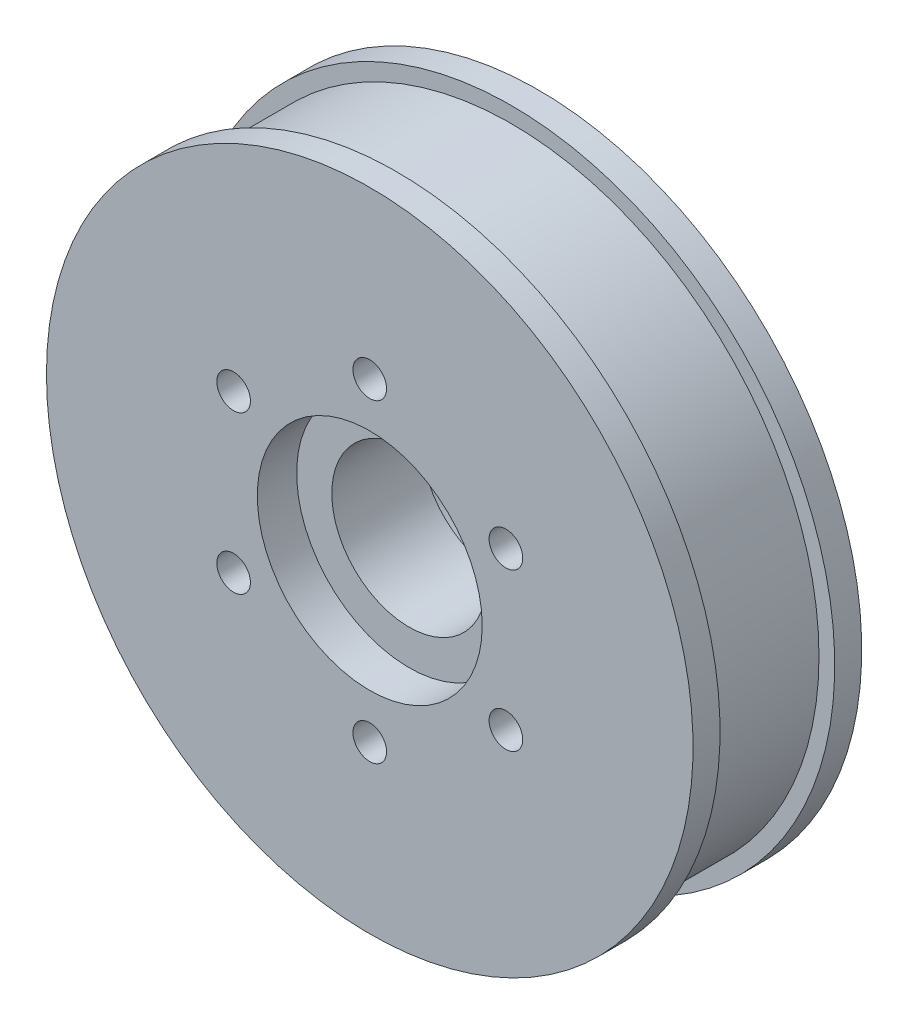
SolidWorks part; units mm, degrees
ref_plane "Front Plane" through (0, 0, 0) normal (0, 0, 1) x (1, 0, 0)
ref_plane "Top Plane" through (0, 0, 0) normal (0, 1, 0) x (1, 0, 0)
ref_plane "Right Plane" through (0, 0, 0) normal (1, 0, 0) x (0, 0, -1)
sketch "Sketch1" plane through (0, 0, 0) normal (0, 0, 1) x (1, 0, 0)
  circle A0 centre (0, 0) radius 36.5125
  dimension "D1" = 73.025
extrude "Boss-Extrude1" add sketch "Sketch1" along normal blind 19.05
sketch "Sketch2" plane through (0, 0, 19.05) normal (0, 0, 1) x (1, 0, 0)
  circle A0 centre (0, 0) radius 8.7312
  dimension "D1" = 17.4625
extrude "Cut-Extrude1" cut sketch "Sketch2" against normal through all
sketch "Sketch3" plane through (0, 0, 19.05) normal (0, 0, 1) x (1, 0, 0)
  circle A0 centre (0, 0) radius 12.7
  dimension "D1" = 25.4
extrude "Cut-Extrude2" cut sketch "Sketch3" against normal blind 4.445
sketch "Sketch4" plane through (0, 0, 0) normal (0, 0, -1) x (-1, 0, 0)
  circle A0 centre (0, 0) radius 12.7
  dimension "D1" = 25.4
extrude "Cut-Extrude3" cut sketch "Sketch4" against normal blind 4.445
sketch "Sketch5" plane through (0, 0, 0) normal (0, 0, -1) x (-1, 0, 0)
  line L0 (0, 0) -> (0, 50.3412)
  line L1 (0, 34.29) -> (2.1586, 36.4486)
  line L2 (0, 34.29) -> (-2.1586, 36.4486)
  circle A0 centre (0, 0) radius 36.5125
  circle A1 centre (0, 0) radius 34.29
  circle A2 centre (0, 0) radius 36.5125 construction
  circle M404 centre (0, 0) radius 36.5125
  dimension "D1" = 68.58
  dimension "D2" = 0
  dimension "D3" = 45
extrude "Cut-Extrude4" [suppressed] cut sketch "Sketch5" against normal through all contours L2 L0 M404 | L0 L1 M404
pattern_circular "CirPattern1" [suppressed] count 45 over 360 of bodies 105
hole_wizard "#6 Clearance Hole1" positions "Sketch8" profile "Sketch9" hole size "#6" standard "ANSI Inch" end condition through all
sketch "Sketch8" plane through (-8.1703, -47.0035, 19.05) normal (0, 0, 1) x (1, 0, 0)
  point P0 (8.1703, 64.7581)
  point P1 (-7.2056, 55.8808)
  point P2 (-7.2056, 38.1262)
  point P4 (8.1703, 29.2489)
  point P6 (23.5462, 38.1262)
  point P8 (23.5462, 55.8808)
sketch "Sketch9" plane through (0, 17.7546, 19.05) normal (1, 0, 0) x (0, -1, 0)
  line L0 (0, 0) -> (0, 19.05)
  line L1 (0, 19.05) -> (1.8986, 19.05)
  line L2 (1.8986, 19.05) -> (1.8986, 0)
  line L5 (1.8986, 0) -> (0, 0)
  line L11 (0, -6.35) -> (0, 107.95) construction
  dimension "Thru Hole Dia." = 3.7973
  dimension "Thru Hole Depth" = 19.05
sketch "Sketch10" plane through (0, 0, 0) normal (1, 0, 0) x (0, 0, -1)
  line L0 (-19.05, 36.5125) -> (-16.002, 36.5125)
  line L1 (0, 36.5125) -> (-19.05, 36.5125) construction
  line L2 (-16.002, 36.5125) -> (-16.002, 34.7345)
  line L3 (-16.002, 34.7345) -> (-3.048, 34.7345)
  line L4 (-3.048, 34.7345) -> (-3.048, 36.5125)
  line L5 (-3.048, 36.5125) -> (0, 36.5125)
  line L6 (0, -36.5125) -> (0, 36.5125) construction
  line L8 (-19.05, 0) -> (0, 0)
  line L11 (-3.048, 36.5125) -> (-3.048, 51.1522)
  line L12 (-3.048, 51.1522) -> (-16.002, 51.1522)
  line L13 (-16.002, 51.1522) -> (-16.002, 36.5125)
  dimension "D1" = 3.048
  dimension "D2" = 3.048
  dimension "D3" = 1.778
revolve "Cut-Revolve1" cut sketch "Sketch10" angle 360 about L8 region at (0, 42.9434, 9.525)
